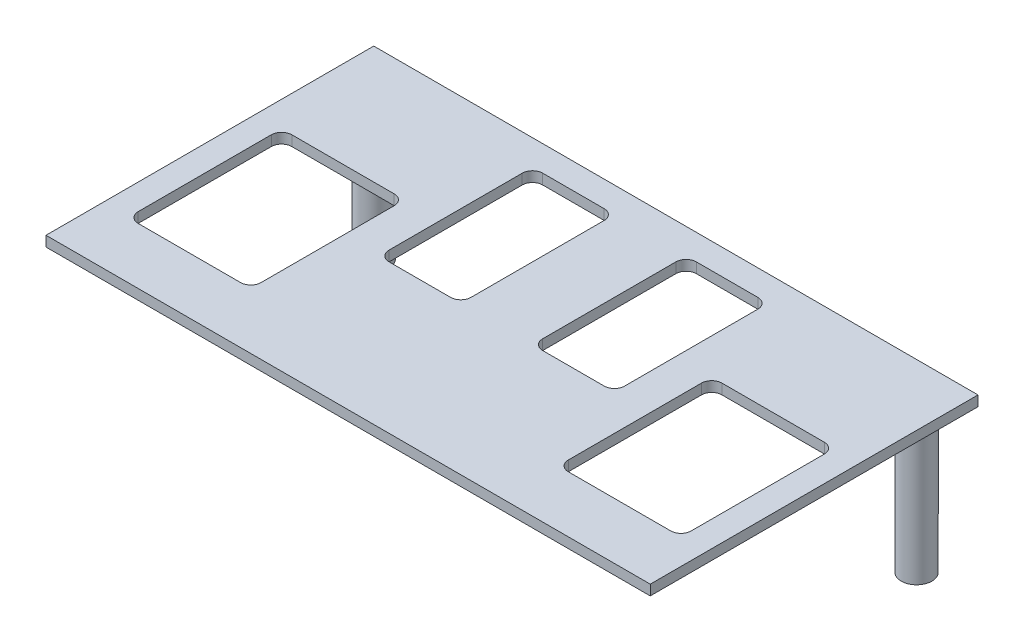
SolidWorks part; units mm, degrees
material "PVC hart"
ref_plane "Ebene vorne" through (0, 0, 0) normal (0, 0, 1) x (1, 0, 0)
ref_plane "Ebene oben" through (0, 0, 0) normal (0, 1, 0) x (1, 0, 0)
ref_plane "Ebene rechts" through (0, 0, 0) normal (1, 0, 0) x (0, 0, -1)
sketch "Skizze1" plane through (0, 0, 0) normal (0, 1, 0) x (1, 0, 0)
  line L1 (-29.5, 16) -> (29.5, 16)
  line L2 (-29.5, 16) -> (-29.5, -16)
  line L3 (-29.5, -16) -> (29.5, -16)
  line L4 (29.5, 16) -> (29.5, -16)
  line L5 (-29.5, 16) -> (29.5, -16) construction
  line L6 (-29.5, -16) -> (29.5, 16) construction
  point P0 (0, 0)
  dimension "D1" = 32
  dimension "D2" = 59
extrude "Aufsatz-Linear austragen1" add sketch "Skizze1" along normal blind 1
sketch "Skizze4" plane through (0, 0, 0) normal (0, -1, 0) x (1, 0, 0)
  line L0 (0, 20.7608) -> (0, -19.573) construction
  line L1 (-29.5, 16) -> (29.5, 16) construction
  circle A0 centre (8, 6) radius 1.55
  circle A1 centre (-8, 6) radius 1.55
  dimension "D1" = 3.1
  dimension "D2" = 10
  dimension "D3" = 16
extrude "Aufsatz-Linear austragen3" add sketch "Skizze4" along normal blind 1.5
sketch "Skizze5" plane through (0, 0, 0) normal (0, -1, 0) x (1, 0, 0)
  line L0 (-8, 6) -> (8, 6) construction
  line L1 (0, 18.925) -> (0, -20.2209) construction
  line L2 (29.5, -16) -> (-29.5, -16) construction
  line L3 (29.5, 16) -> (29.5, -16) construction
  circle A0 centre (26.5, -13) radius 1.5
  circle A1 centre (-26.5, -13) radius 1.5
  dimension "D1" = 3
  dimension "D2" = 3
  dimension "D3" = 3
extrude "Aufsatz-Linear austragen4" add sketch "Skizze5" along normal blind 14
fillet "Verrundung3" radius 1 2 edges at (-26.5, 0, -11.5) (26.5, 0, -11.5)
sketch "Skizze6" plane through (0, 0, 0) normal (0, -1, 0) x (1, 0, 0)
  line L0 (0, 22.1647) -> (0, -25.0804) construction
  line L1 (-29.5, 16) -> (29.5, 16) construction
  line L2 (16, 10.5) -> (26, 10.5)
  line L3 (15, 9.5) -> (15, -3.5)
  line L4 (16, -4.5) -> (26, -4.5)
  line L5 (27, 9.5) -> (27, -3.5)
  line L6 (15, 10.5) -> (27, -4.5) construction
  line L7 (15, -4.5) -> (27, 10.5) construction
  line L8 (4.5, 1.5) -> (10.5, 1.5)
  line L9 (3.5, 0.5) -> (3.5, -12.5)
  line L10 (4.5, -13.5) -> (10.5, -13.5)
  line L11 (11.5, 0.5) -> (11.5, -12.5)
  line L12 (3.5, 1.5) -> (11.5, -13.5) construction
  line L13 (3.5, -13.5) -> (11.5, 1.5) construction
  line L14 (29.5, -16) -> (-29.5, -16) construction
  line L15 (-3.5, -13.5) -> (-11.5, 1.5) construction
  line L16 (-3.5, 1.5) -> (-11.5, -13.5) construction
  line L21 (-15, -4.5) -> (-27, 10.5) construction
  line L22 (-15, 10.5) -> (-27, -4.5) construction
  line L27 (-11.5, 0.5) -> (-11.5, -12.5)
  line L28 (-4.5, -13.5) -> (-10.5, -13.5)
  line L29 (-3.5, 0.5) -> (-3.5, -12.5)
  line L30 (-4.5, 1.5) -> (-10.5, 1.5)
  line L31 (-27, 9.5) -> (-27, -3.5)
  line L32 (-16, -4.5) -> (-26, -4.5)
  line L33 (-15, 9.5) -> (-15, -3.5)
  line L34 (-16, 10.5) -> (-26, 10.5)
  arc A0 (10.5, -13.5) -> (11.5, -12.5) centre (10.5, -12.5) ccw
  arc A1 (3.5, -12.5) -> (4.5, -13.5) centre (4.5, -12.5) ccw
  arc A2 (4.5, 1.5) -> (3.5, 0.5) centre (4.5, 0.5) ccw
  arc A3 (10.5, 1.5) -> (11.5, 0.5) centre (10.5, 0.5) cw
  arc A4 (15, -3.5) -> (16, -4.5) centre (16, -3.5) ccw
  arc A5 (26, -4.5) -> (27, -3.5) centre (26, -3.5) ccw
  arc A6 (26, 10.5) -> (27, 9.5) centre (26, 9.5) cw
  arc A7 (16, 10.5) -> (15, 9.5) centre (16, 9.5) ccw
  arc A16 (-16, 10.5) -> (-15, 9.5) centre (-16, 9.5) cw
  arc A17 (-26, 10.5) -> (-27, 9.5) centre (-26, 9.5) ccw
  arc A18 (-26, -4.5) -> (-27, -3.5) centre (-26, -3.5) cw
  arc A19 (-15, -3.5) -> (-16, -4.5) centre (-16, -3.5) cw
  arc A20 (-10.5, 1.5) -> (-11.5, 0.5) centre (-10.5, 0.5) ccw
  arc A21 (-4.5, 1.5) -> (-3.5, 0.5) centre (-4.5, 0.5) cw
  arc A22 (-3.5, -12.5) -> (-4.5, -13.5) centre (-4.5, -12.5) cw
  arc A23 (-10.5, -13.5) -> (-11.5, -12.5) centre (-10.5, -12.5) cw
  point P3 (21, 3)
  point P8 (7.5, -6)
  point P76 (-7.5, -6)
  point P77 (-21, 3)
  dimension "D9" = 1
  dimension "D1" = 13
  dimension "D2" = 10
  dimension "D4" = 8
  dimension "D5" = 7.5
  dimension "D6" = 15
  dimension "D7" = 12
  dimension "D8" = 21
extrude "Schnitt-Linear austragen2" cut sketch "Skizze6" against normal up to surface (1 mm away) up to face at (0, 1, 0)
chamfer "Fase1" distance 0.2 angle 45 2 edges at (8, -1.5, 4.45) (-8, -1.5, 7.55)
